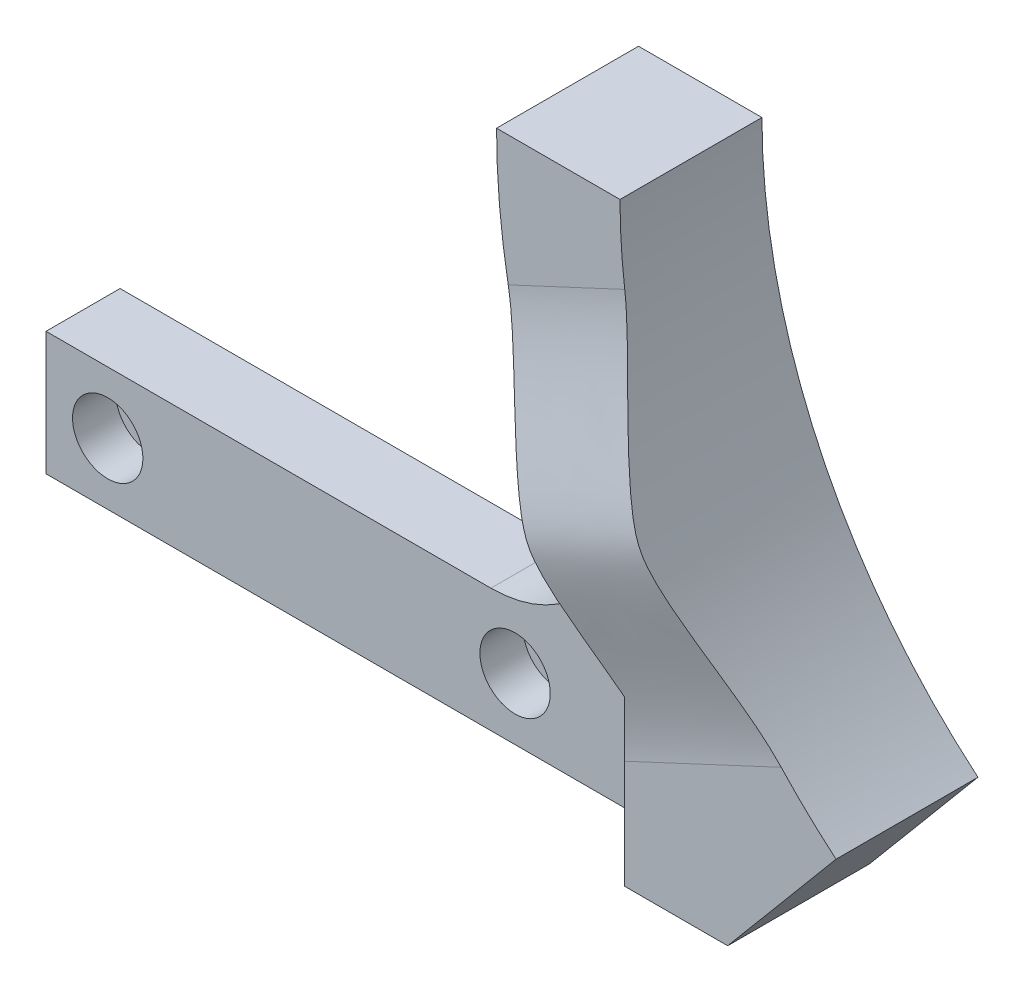
SolidWorks part; units mm, degrees
ref_plane "Front Plane" through (0, 0, 0) normal (1, 0, 0) x (0, 1, 0)
ref_plane "Top Plane" through (0, 0, 0) normal (0, 0, 1) x (0, 1, 0)
ref_plane "Right Plane" through (0, 0, 0) normal (0, 1, 0) x (-1, 0, 0)
sketch "Sketch1" plane through (0, 0, 0) normal (0, 0, 1) x (0, 1, 0)
  line L0 (0, 0) -> (-37.5362, 31.4966) construction
  line L1 (0, 0) -> (0, 49) construction
  line L2 (-37.5362, 31.4966) -> (-40.2173, 33.7463)
  line L3 (0, 49) -> (0, 52.5)
  line L4 (0, 0) -> (-22.1875, 47.5812) construction
  line L5 (0, 52.5) -> (0, 59)
  line L6 (-48, 101) -> (-38, 101)
  line L7 (-48, 101) -> (-48, 45.1331)
  line L8 (-48, 45.1331) -> (-38, 45.1331)
  line L9 (-38, 101) -> (-38, 45.1331)
  line L10 (-40.2173, 33.7463) -> (-48, 40.2768)
  line L11 (-48, 40.2768) -> (-48, 45.1331)
  circle A0 centre (-43, 63) radius 1.6
  circle A1 centre (-43, 96) radius 1.6
  circle A2 centre (0, 0) radius 45 construction
  arc A3 (-37.5362, 31.4966) -> (0, 49) centre (0, 0) ccw construction
  arc A4 (0, 52.5) -> (-22.1875, 47.5812) centre (0, 0) ccw construction
  arc A5 (-40.2173, 33.7463) -> (0, 52.5) centre (0, 0) ccw construction
  arc A6 (0, 49) -> (-37.5362, 31.4966) centre (0, 0) ccw
  arc A7 (-22.1875, 47.5812) -> (-40.2173, 33.7463) centre (0, 0) ccw construction
  circle A8 centre (-43, 63) radius 2.85
  circle A9 centre (-43, 96) radius 2.85
  arc A10 (0, 59) -> (-38, 45.1331) centre (0, 0) ccw
  dimension "D1" = 3.2
  dimension "D2" = 3.2
  dimension "D6" = 90
  dimension "D7" = 98
  dimension "D8" = 105
  dimension "D14" = 5.7
  dimension "D15" = 5.7
  dimension "D3" = 33
  dimension "D4" = 43
  dimension "D5" = 63
  dimension "D9" = 25
  dimension "D10" = 25
  dimension "D11" = 5
  dimension "D12" = 10
  dimension "D13" = 5
  dimension "D16" = 10
extrude "Boss-Extrude1" add sketch "Sketch1" along normal blind 16 contours L8 L11 A6 L3 region at (-47.1318, -23.9574, 0)
extrude "Boss-Extrude2" add sketch "Sketch1<3>" along normal blind 6 contours L9 L6 L7 L8 A9 A8 region at (-72.4198, -43, 0)
sketch "Sketch1<3>" plane through (0, 0, 0) normal (0, 0, 1) x (0, 1, 0) same geometry as "Sketch1"
extrude "Boss-Extrude3" add sketch "Sketch1<4>" along normal offset from surface (2.5 mm away) 3.5 contours A9 A1 | A8 A0 region at (-63, -45.7694, 0) region at (-96, -45.7694, 0) up to face at (-93.15, -43, 6)
sketch "Sketch1<4>" plane through (0, 0, 0) normal (0, 0, 1) x (0, 1, 0) same geometry as "Sketch1"
chamfer "Chamfer3" distance 15 angle 45 1 edges at (-45.1331, -38, 3) first distance on face at (-52.0232, -23.2902, 7.6)
chamfer "Chamfer4" distance 9 angle 45 1 edges at (-45.1331, -43, 6)
ref_plane "Plane1" through (-40.2483, -18.7681, 0) normal (0.9063, 0.4226, 0) x (0, 0, -1)
sketch "Sketch3" plane through (-40.2483, -18.7681, 0) normal (0.9063, 0.4226, 0) x (0, 0, -1)
  line L0 (-11.5, 34.7824) -> (-11.5, -42.7172) construction
  line L1 (0, -20.7083) -> (0, 20.7083) construction
  line L2 (-14.5, -20.7083) -> (0, -20.7083) construction
  line L3 (-14.5, 6.1235) -> (-14.5, 1.3951) construction
  line L4 (-11.5, 12.8992) -> (-11.5, 7.1782) construction
  line L5 (-11.5, -12.3215) -> (-11.5, -19.1417) construction
  line L6 (-11.5, -15) -> (-11.5, -26.4811)
  line L7 (-16, -26.4811) -> (0, -26.4811) construction
  line L8 (-11.5, -26.4811) -> (-21.9403, -26.4811)
  line L9 (-21.9403, -26.4811) -> (-21.9403, 24.9345)
  line L10 (-11.5, 15) -> (-11.5, 24.9345)
  line L11 (-11.5, 24.9345) -> (-21.9403, 24.9345)
  line L12 (-16, 24.9345) -> (0, 24.9345) construction
  line L13 (-14.5, 24.9345) -> (-14.5, 20.7083) construction
  line L14 (-14.5, 20.7083) -> (-14.5, -20.7083) construction
  line L15 (-14.5, -20.7083) -> (-14.5, -26.4811) construction
  line L16 (-14.5, 20.7083) -> (0, 20.7083) construction
  spline S0 degree 3 poles (-11.5, -15) (-11.5, -10.5) (-14.4363, -3.2355) (-14.6024, 2.675) (-11.5, 10.5) (-11.5, 15) knots 0 0 0 0 0.483457 0.583457 1 1 1 1
  point P42 (-14.5, 0)
  dimension "D2" = 15
  dimension "D3" = 15
  dimension "D5" = 20
  dimension "D1" = 11.5
  dimension "D4" = 30
  dimension "D6" = 15
  dimension "D7" = 3
extrude "Cut-Extrude2" cut sketch "Sketch3" against normal blind 27.5 contours L6 S0 L10 L11 L9 L8 region at (-39.8942, -19.5275, 17.0703)
fillet "Fillet1" radius 10 1 edges at (-55.7787, -38, 3)
equation "\"D10@Sketch1\"=\"D9@Sketch1\""
equation "\"D3@Sketch3\"=\"D2@Sketch3\""
